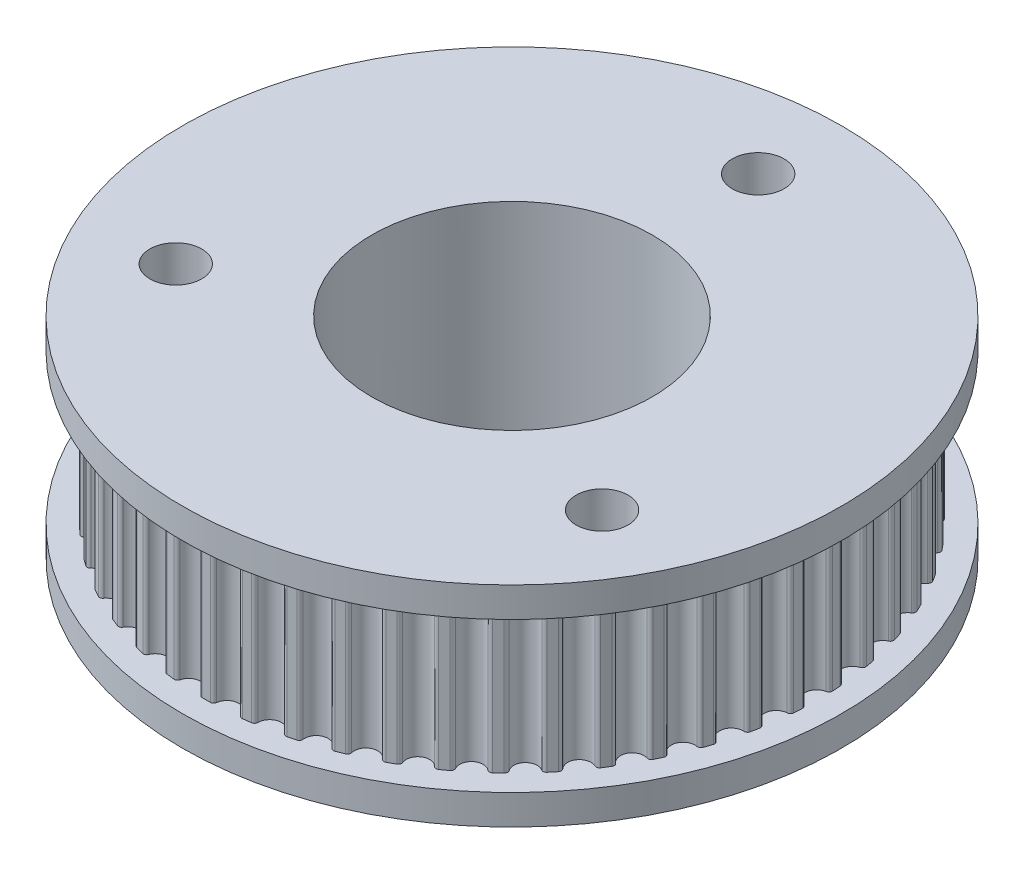
SolidWorks part; units mm, degrees
ref_plane "Front Plane" through (0, 0, 0) normal (0, 0, 1) x (1, 0, 0)
ref_plane "Top Plane" through (0, 0, 0) normal (0, 1, 0) x (1, 0, 0)
ref_plane "Right Plane" through (0, 0, 0) normal (1, 0, 0) x (0, 0, -1)
sketch "mountingHoles" plane through (0, 0, 0) normal (0, 1, 0) x (1, 0, 0)
  line L0 (0, 28.0035) -> (0, 17.8435) construction
  circle A0 centre (0, 0) radius 39.751
  circle A2 centre (0, 31.3055) radius 3.302
  circle A6 centre (27.1114, -15.6527) radius 3.302
  circle A10 centre (-27.1114, -15.6528) radius 3.302
  circle A11 centre (0, 0) radius 17.8435
  circle A13 centre (27.1114, 15.6528) radius 3.302 [skipped]
  circle A14 centre (-27.1114, 15.6527) radius 3.302 [skipped]
  circle A15 centre (0, -31.3055) radius 3.302 [skipped]
  point P26 (0, 0)
  dimension "D1" = 79.502
  dimension "D2" = 35.687
  dimension "D3" = 10.16
  dimension "D4" = 6.604
  dimension "D5" = 6
extrude "Boss-Extrude1" add sketch "mountingHoles" along normal mid plane 19.05 contours A0
sketch "Sketch2" plane through (0, 9.525, 0) normal (0, 1, 0) x (1, 0, 0)
  line L0 (0, 0) -> (0, 39.4817) construction
  line L1 (0, 0) -> (2.4339, 38.6854) construction
  line L2 (0, 38.8874) -> (0, 39.751)
  line L3 (2.4339, 38.6854) -> (2.496, 39.6726) construction
  line L4 (4.8739, 38.5808) -> (4.9821, 39.4376)
  arc A0 (0, 38.8874) -> (0.5234, 38.8839) centre (0, 0) cw
  arc A1 (0.5234, 38.8839) -> (0.9463, 38.5043) centre (0.5176, 38.4521) cw
  arc A2 (0.9463, 38.5043) -> (3.8871, 38.3193) centre (2.4339, 38.6854) ccw
  circle A3 centre (0, 0) radius 39.751 construction
  arc A4 (4.3541, 38.6429) -> (3.8871, 38.3193) centre (4.3058, 38.2138) ccw
  arc A5 (4.8739, 38.5808) -> (4.3541, 38.6429) centre (0, 0) ccw
  arc A6 (0, 39.751) -> (4.9821, 39.4376) centre (0, 0) cw
  dimension "D3" = 0.8636
  dimension "D4" = 3.6
  dimension "D2" = 1.4986
  dimension "D1" = 0.4318
extrude "Cut-Extrude1" cut sketch "Sketch2" against normal blind 19.05 contours A6 L4 A5 A4 A2 A1 A0 L2
pattern_circular "CirPattern1" count 50 over 360 about axis through (0, 9.525, 0) along (0, -1, 0) of "Cut-Extrude1" reverse direction yes
sketch "flange" plane through (0, 9.525, 0) normal (0, 1, 0) x (1, 0, 0)
  circle A0 centre (0, 0) radius 41.91
extrude "Boss-Extrude2" add sketch "flange" along normal blind 3.81 contours A0
sketch "Sketch6" plane through (0, -9.525, 0) normal (0, -1, 0) x (1, 0, 0)
  circle A0 centre (0, 0) radius 41.91
extrude "Boss-Extrude3" add sketch "Sketch6" along normal blind 3.81
extrude "Cut-Extrude5" cut sketch "Sketch1<5>" against normal blind 31.242 and the other way blind 32.512 contours A2 | A11 | A6 | A10
sketch "Sketch1<5>" plane through (0, 0, 0) normal (0, 1, 0) x (1, 0, 0) same geometry as "mountingHoles"
equation "\"n\"= 50"
equation "\"p\"= 5mm"
equation "\"pd\"= \"n\" * \"p\" / 3.1415926"
